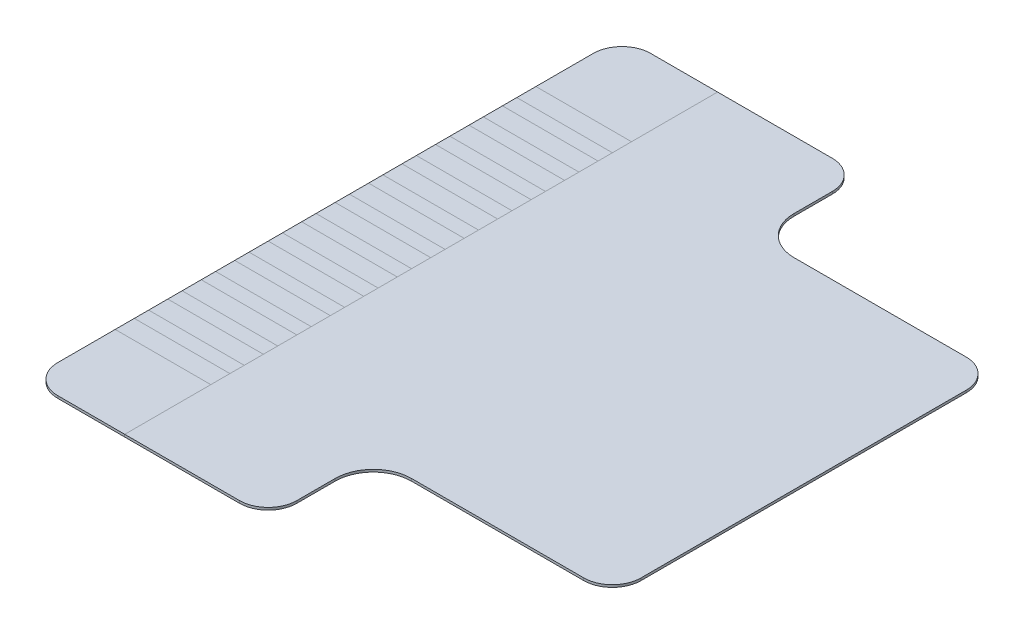
SolidWorks part; units mm, degrees
ref_plane "Front Plane" through (0, 0, 0) normal (0, 0, 1) x (1, 0, 0)
ref_plane "Top Plane" through (0, 0, 0) normal (0, 1, 0) x (1, 0, 0)
ref_plane "Right Plane" through (0, 0, 0) normal (1, 0, 0) x (0, 0, -1)
sketch "草图1" plane through (0, 0, 0) normal (0, 1, 0) x (1, 0, 0)
  line L0 (-7.3028, 0.9) -> (-7.3028, 0.5)
  line L1 (-6.7028, 6.2) -> (-2.9028, 6.2)
  line L2 (-7.3028, 5.6) -> (-7.3028, -5.6)
  line L3 (-6.7028, -6.2) -> (-2.9028, -6.2)
  line L4 (-2.3028, 5.6) -> (-2.3028, 4.8)
  line L5 (-1.5028, 4) -> (2.0972, 4)
  line L7 (-1.5028, -4) -> (2.0972, -4)
  line L8 (2.6972, 3.4) -> (2.6972, -3.4)
  line L9 (-7.3028, 0.2) -> (-5.3028, 0.2)
  line L10 (-7.3028, 0.2) -> (-7.3028, -0.2)
  line L11 (-7.3028, -0.2) -> (-5.3028, -0.2)
  line L12 (-5.3028, 0.2) -> (-5.3028, -0.2)
  line L13 (-7.3028, 0.9) -> (-5.3028, 0.9)
  line L14 (-5.3028, 0.9) -> (-5.3028, 0.5)
  line L15 (-7.3028, 0.5) -> (-5.3028, 0.5)
  line L16 (-7.3028, 1.6) -> (-7.3028, 1.2)
  line L17 (-7.3028, 1.6) -> (-5.3028, 1.6)
  line L18 (-5.3028, 1.6) -> (-5.3028, 1.2)
  line L19 (-7.3028, 1.2) -> (-5.3028, 1.2)
  line L20 (-7.3028, 2.3) -> (-7.3028, 1.9)
  line L21 (-7.3028, 2.3) -> (-5.3028, 2.3)
  line L22 (-5.3028, 2.3) -> (-5.3028, 1.9)
  line L23 (-7.3028, 1.9) -> (-5.3028, 1.9)
  line L24 (-7.3028, 3) -> (-7.3028, 2.6)
  line L25 (-7.3028, 3) -> (-5.3028, 3)
  line L26 (-5.3028, 3) -> (-5.3028, 2.6)
  line L27 (-7.3028, 2.6) -> (-5.3028, 2.6)
  line L28 (-7.3028, 3.7) -> (-7.3028, 3.3)
  line L29 (-7.3028, 3.7) -> (-5.3028, 3.7)
  line L30 (-5.3028, 3.7) -> (-5.3028, 3.3)
  line L31 (-7.3028, 3.3) -> (-5.3028, 3.3)
  line L32 (-7.3028, 4.4) -> (-7.3028, 4)
  line L33 (-7.3028, 4.4) -> (-5.3028, 4.4)
  line L34 (-5.3028, 4.4) -> (-5.3028, 4)
  line L35 (-7.3028, 4) -> (-5.3028, 4)
  line L36 (-7.3028, 0.2) -> (-7.3028, -0.2)
  line L37 (-7.3028, 0.2) -> (-5.3028, 0.2)
  line L38 (-5.3028, 0.2) -> (-5.3028, -0.2)
  line L39 (-7.3028, -0.2) -> (-5.3028, -0.2)
  line L40 (-7.3028, 0.9) -> (-7.3028, 0.5)
  line L41 (-7.3028, 0.9) -> (-5.3028, 0.9)
  line L42 (-5.3028, 0.9) -> (-5.3028, 0.5)
  line L43 (-7.3028, 0.5) -> (-5.3028, 0.5)
  line L44 (-7.3028, 1.6) -> (-7.3028, 1.2)
  line L45 (-7.3028, 1.6) -> (-5.3028, 1.6)
  line L46 (-5.3028, 1.6) -> (-5.3028, 1.2)
  line L47 (-7.3028, 1.2) -> (-5.3028, 1.2)
  line L48 (-7.3028, 2.3) -> (-7.3028, 1.9)
  line L49 (-7.3028, 2.3) -> (-5.3028, 2.3)
  line L50 (-5.3028, 2.3) -> (-5.3028, 1.9)
  line L51 (-7.3028, 1.9) -> (-5.3028, 1.9)
  line L52 (-7.3028, 3) -> (-7.3028, 2.6)
  line L53 (-7.3028, 3) -> (-5.3028, 3)
  line L54 (-5.3028, 3) -> (-5.3028, 2.6)
  line L55 (-7.3028, 2.6) -> (-5.3028, 2.6)
  line L56 (-7.3028, 3.7) -> (-7.3028, 3.3)
  line L57 (-7.3028, 3.7) -> (-5.3028, 3.7)
  line L58 (-5.3028, 3.7) -> (-5.3028, 3.3)
  line L59 (-7.3028, 3.3) -> (-5.3028, 3.3)
  line L60 (-7.3028, -0.5) -> (-7.3028, -0.9)
  line L61 (-7.3028, -0.5) -> (-5.3028, -0.5)
  line L62 (-5.3028, -0.5) -> (-5.3028, -0.9)
  line L63 (-7.3028, -0.9) -> (-5.3028, -0.9)
  line L64 (-7.3028, 0.2) -> (-7.3028, -0.2)
  line L65 (-7.3028, 0.2) -> (-5.3028, 0.2)
  line L66 (-5.3028, 0.2) -> (-5.3028, -0.2)
  line L67 (-7.3028, -0.2) -> (-5.3028, -0.2)
  line L68 (-7.3028, 0.9) -> (-7.3028, 0.5)
  line L69 (-7.3028, 0.9) -> (-5.3028, 0.9)
  line L70 (-5.3028, 0.9) -> (-5.3028, 0.5)
  line L71 (-7.3028, 0.5) -> (-5.3028, 0.5)
  line L72 (-7.3028, 1.6) -> (-7.3028, 1.2)
  line L73 (-7.3028, 1.6) -> (-5.3028, 1.6)
  line L74 (-5.3028, 1.6) -> (-5.3028, 1.2)
  line L75 (-7.3028, 1.2) -> (-5.3028, 1.2)
  line L76 (-7.3028, 2.3) -> (-7.3028, 1.9)
  line L77 (-7.3028, 2.3) -> (-5.3028, 2.3)
  line L78 (-5.3028, 2.3) -> (-5.3028, 1.9)
  line L79 (-7.3028, 1.9) -> (-5.3028, 1.9)
  line L80 (-7.3028, 3) -> (-7.3028, 2.6)
  line L81 (-7.3028, 3) -> (-5.3028, 3)
  line L82 (-5.3028, 3) -> (-5.3028, 2.6)
  line L83 (-7.3028, 2.6) -> (-5.3028, 2.6)
  line L84 (-7.3028, -1.2) -> (-7.3028, -1.6)
  line L85 (-7.3028, -1.2) -> (-5.3028, -1.2)
  line L86 (-5.3028, -1.2) -> (-5.3028, -1.6)
  line L87 (-7.3028, -1.6) -> (-5.3028, -1.6)
  line L88 (-7.3028, -0.5) -> (-7.3028, -0.9)
  line L89 (-7.3028, -0.5) -> (-5.3028, -0.5)
  line L90 (-5.3028, -0.5) -> (-5.3028, -0.9)
  line L91 (-7.3028, -0.9) -> (-5.3028, -0.9)
  line L92 (-7.3028, 0.2) -> (-7.3028, -0.2)
  line L93 (-7.3028, 0.2) -> (-5.3028, 0.2)
  line L94 (-5.3028, 0.2) -> (-5.3028, -0.2)
  line L95 (-7.3028, -0.2) -> (-5.3028, -0.2)
  line L96 (-7.3028, 0.9) -> (-7.3028, 0.5)
  line L97 (-7.3028, 0.9) -> (-5.3028, 0.9)
  line L98 (-5.3028, 0.9) -> (-5.3028, 0.5)
  line L99 (-7.3028, 0.5) -> (-5.3028, 0.5)
  line L100 (-7.3028, 1.6) -> (-7.3028, 1.2)
  line L101 (-7.3028, 1.6) -> (-5.3028, 1.6)
  line L102 (-5.3028, 1.6) -> (-5.3028, 1.2)
  line L103 (-7.3028, 1.2) -> (-5.3028, 1.2)
  line L104 (-7.3028, 2.3) -> (-7.3028, 1.9)
  line L105 (-7.3028, 2.3) -> (-5.3028, 2.3)
  line L106 (-5.3028, 2.3) -> (-5.3028, 1.9)
  line L107 (-7.3028, 1.9) -> (-5.3028, 1.9)
  line L108 (-7.3028, -1.9) -> (-7.3028, -2.3)
  line L109 (-7.3028, -1.9) -> (-5.3028, -1.9)
  line L110 (-5.3028, -1.9) -> (-5.3028, -2.3)
  line L111 (-7.3028, -2.3) -> (-5.3028, -2.3)
  line L112 (-7.3028, -1.2) -> (-7.3028, -1.6)
  line L113 (-7.3028, -1.2) -> (-5.3028, -1.2)
  line L114 (-5.3028, -1.2) -> (-5.3028, -1.6)
  line L115 (-7.3028, -1.6) -> (-5.3028, -1.6)
  line L116 (-7.3028, -0.5) -> (-7.3028, -0.9)
  line L117 (-7.3028, -0.5) -> (-5.3028, -0.5)
  line L118 (-5.3028, -0.5) -> (-5.3028, -0.9)
  line L119 (-7.3028, -0.9) -> (-5.3028, -0.9)
  line L120 (-7.3028, 0.2) -> (-7.3028, -0.2)
  line L121 (-7.3028, 0.2) -> (-5.3028, 0.2)
  line L122 (-5.3028, 0.2) -> (-5.3028, -0.2)
  line L123 (-7.3028, -0.2) -> (-5.3028, -0.2)
  line L124 (-7.3028, 0.9) -> (-7.3028, 0.5)
  line L125 (-7.3028, 0.9) -> (-5.3028, 0.9)
  line L126 (-5.3028, 0.9) -> (-5.3028, 0.5)
  line L127 (-7.3028, 0.5) -> (-5.3028, 0.5)
  line L128 (-7.3028, 1.6) -> (-7.3028, 1.2)
  line L129 (-7.3028, 1.6) -> (-5.3028, 1.6)
  line L130 (-5.3028, 1.6) -> (-5.3028, 1.2)
  line L131 (-7.3028, 1.2) -> (-5.3028, 1.2)
  line L132 (-7.3028, -2.6) -> (-7.3028, -3)
  line L133 (-7.3028, -2.6) -> (-5.3028, -2.6)
  line L134 (-5.3028, -2.6) -> (-5.3028, -3)
  line L135 (-7.3028, -3) -> (-5.3028, -3)
  line L136 (-7.3028, -1.9) -> (-7.3028, -2.3)
  line L137 (-7.3028, -1.9) -> (-5.3028, -1.9)
  line L138 (-5.3028, -1.9) -> (-5.3028, -2.3)
  line L139 (-7.3028, -2.3) -> (-5.3028, -2.3)
  line L140 (-7.3028, -1.2) -> (-7.3028, -1.6)
  line L141 (-7.3028, -1.2) -> (-5.3028, -1.2)
  line L142 (-5.3028, -1.2) -> (-5.3028, -1.6)
  line L143 (-7.3028, -1.6) -> (-5.3028, -1.6)
  line L144 (-7.3028, -0.5) -> (-7.3028, -0.9)
  line L145 (-7.3028, -0.5) -> (-5.3028, -0.5)
  line L146 (-5.3028, -0.5) -> (-5.3028, -0.9)
  line L147 (-7.3028, -0.9) -> (-5.3028, -0.9)
  line L148 (-7.3028, 0.2) -> (-7.3028, -0.2)
  line L149 (-7.3028, 0.2) -> (-5.3028, 0.2)
  line L150 (-5.3028, 0.2) -> (-5.3028, -0.2)
  line L151 (-7.3028, -0.2) -> (-5.3028, -0.2)
  line L152 (-7.3028, 0.9) -> (-7.3028, 0.5)
  line L153 (-7.3028, 0.9) -> (-5.3028, 0.9)
  line L154 (-5.3028, 0.9) -> (-5.3028, 0.5)
  line L155 (-7.3028, 0.5) -> (-5.3028, 0.5)
  line L156 (-7.3028, -3.3) -> (-7.3028, -3.7)
  line L157 (-7.3028, -3.3) -> (-5.3028, -3.3)
  line L158 (-5.3028, -3.3) -> (-5.3028, -3.7)
  line L159 (-7.3028, -3.7) -> (-5.3028, -3.7)
  line L160 (-7.3028, -2.6) -> (-7.3028, -3)
  line L161 (-7.3028, -2.6) -> (-5.3028, -2.6)
  line L162 (-5.3028, -2.6) -> (-5.3028, -3)
  line L163 (-7.3028, -3) -> (-5.3028, -3)
  line L164 (-7.3028, -1.9) -> (-7.3028, -2.3)
  line L165 (-7.3028, -1.9) -> (-5.3028, -1.9)
  line L166 (-5.3028, -1.9) -> (-5.3028, -2.3)
  line L167 (-7.3028, -2.3) -> (-5.3028, -2.3)
  line L168 (-7.3028, -1.2) -> (-7.3028, -1.6)
  line L169 (-7.3028, -1.2) -> (-5.3028, -1.2)
  line L170 (-5.3028, -1.2) -> (-5.3028, -1.6)
  line L171 (-7.3028, -1.6) -> (-5.3028, -1.6)
  line L172 (-7.3028, -0.5) -> (-7.3028, -0.9)
  line L173 (-7.3028, -0.5) -> (-5.3028, -0.5)
  line L174 (-5.3028, -0.5) -> (-5.3028, -0.9)
  line L175 (-7.3028, -0.9) -> (-5.3028, -0.9)
  line L176 (-7.3028, 0.2) -> (-7.3028, -0.2)
  line L177 (-7.3028, 0.2) -> (-5.3028, 0.2)
  line L178 (-5.3028, 0.2) -> (-5.3028, -0.2)
  line L179 (-7.3028, -0.2) -> (-5.3028, -0.2)
  line L180 (-7.3028, -0.5) -> (-7.3028, -0.9)
  line L181 (-7.3028, -0.5) -> (-5.3028, -0.5)
  line L182 (-5.3028, -0.5) -> (-5.3028, -0.9)
  line L183 (-7.3028, -0.9) -> (-5.3028, -0.9)
  line L184 (-7.3028, -1.2) -> (-7.3028, -1.6)
  line L185 (-7.3028, -1.2) -> (-5.3028, -1.2)
  line L186 (-5.3028, -1.2) -> (-5.3028, -1.6)
  line L187 (-7.3028, -1.6) -> (-5.3028, -1.6)
  line L188 (-7.3028, -1.9) -> (-7.3028, -2.3)
  line L189 (-7.3028, -1.9) -> (-5.3028, -1.9)
  line L190 (-5.3028, -1.9) -> (-5.3028, -2.3)
  line L191 (-7.3028, -2.3) -> (-5.3028, -2.3)
  line L192 (-7.3028, -2.6) -> (-7.3028, -3)
  line L193 (-7.3028, -2.6) -> (-5.3028, -2.6)
  line L194 (-5.3028, -2.6) -> (-5.3028, -3)
  line L195 (-7.3028, -3) -> (-5.3028, -3)
  line L196 (-7.3028, -3.3) -> (-7.3028, -3.7)
  line L197 (-7.3028, -3.3) -> (-5.3028, -3.3)
  line L198 (-5.3028, -3.3) -> (-5.3028, -3.7)
  line L199 (-7.3028, -3.7) -> (-5.3028, -3.7)
  line L200 (-7.3028, -4) -> (-7.3028, -4.4)
  line L201 (-7.3028, -4) -> (-5.3028, -4)
  line L202 (-5.3028, -4) -> (-5.3028, -4.4)
  line L203 (-7.3028, -4.4) -> (-5.3028, -4.4)
  line L204 (-2.3028, -4.8) -> (-2.3028, -5.6)
  line L205 (-5.3028, 6.2) -> (-5.3028, -6.2)
  arc A0 (2.0972, -4) -> (2.6972, -3.4) centre (2.0972, -3.4) ccw
  arc A1 (2.0972, 4) -> (2.6972, 3.4) centre (2.0972, 3.4) cw
  arc A2 (-2.9028, 6.2) -> (-2.3028, 5.6) centre (-2.9028, 5.6) cw
  arc A3 (-2.9028, -6.2) -> (-2.3028, -5.6) centre (-2.9028, -5.6) ccw
  arc A4 (-7.3028, -5.6) -> (-6.7028, -6.2) centre (-6.7028, -5.6) ccw
  arc A5 (-6.7028, 6.2) -> (-7.3028, 5.6) centre (-6.7028, 5.6) ccw
  arc A6 (-2.3028, -4.8) -> (-1.5028, -4) centre (-1.5028, -4.8) cw
  arc A7 (-1.5028, 4) -> (-2.3028, 4.8) centre (-1.5028, 4.8) cw
  point P12 (-5.3028, 0)
  point P14 (-7.3028, 0)
  point P15 (2.6972, 0)
  point P212 (2.6972, 4)
  point P215 (-2.3028, 6.2)
  point P220 (-7.3028, -6.2)
  point P223 (-7.3028, 6.2)
  point P228 (-2.3028, 4)
  dimension "D8" = 0.6
  dimension "D9" = 0.8
  dimension "D1" = 12.4
  dimension "D2" = 2
  dimension "D3" = 0.4
  dimension "D6" = 5
  dimension "D7" = 5
  dimension "D10" = 8
  dimension "D4" = 7
  dimension "D5" = 7
extrude "凸台-拉伸1" add sketch "草图1" along normal blind 0.05 contours L5 A7 L4 A2 L1 A5 L2 L33 L34 L35 L29 L30 L31 L25 L26 L27 L21 L22 L23 L17 L18 L19 L13 L14 L15 L9 L12 L11 L61 L62 L63 L85 L86 L87 L109 L110 L111 L133 L134 L135 region at (-1.7388, 0, 0)
extrude "凸台-拉伸2" add sketch "草图1<3>" along normal blind 0.05 separate body contours L2 L35 L34 L33 | L2 L31 L30 L29 | L2 L27 L26 L25 | L2 L23 L22 L21 | L2 L19 L18 L17 | L0 L15 L14 L13 | L12 L9 L2 L11 | L2 L63 L62 L61 | L2 L87 L86 L85 | L2 L111 L110 L109 | L2 L135 L134 L133 | L2 L159 L158 L157 | L201 L202 L203 L200 region at (-6.3028, 0, -0.7) region at (-6.3028, 0, -1.4) region at (-6.3028, 0, 0) region at (-6.3028, 0, -2.1) region at (-6.3028, 0, 0.7) region at (-6.3028, 0, -2.8) region at (-6.3028, 0, 1.4) region at (-6.3028, 0, -3.5) region at (-6.3028, 0, 2.1) region at (-6.3028, 0, -4.2) region at (-6.3028, 0, 2.8) region at (-6.3028, 0, 3.5)
sketch "草图1<3>" plane through (0, 0, 0) normal (0, 1, 0) x (1, 0, 0) same geometry as "草图1"
extrude "凸台-拉伸3" add sketch "草图1<5>" along normal blind 0.05 separate body contours L2 A4 L3 L205 L203 | L205 L159 L2 L201 | L205 L135 L2 L157 | L205 L111 L2 L133 | L205 L87 L2 L109 | L205 L63 L2 L85 | L205 L11 L2 L61 | L205 L15 L2 L9 | L205 L19 L2 L13 | L205 L23 L2 L17 | L1 A5 L2 L33 L205 | L205 L35 L2 L29 | L205 L31 L2 L25 | L205 L27 L2 L21 region at (-6.3028, 0, -1.05) region at (-6.3028, 0, -0.35) region at (-6.3028, 0, -1.75) region at (-6.3028, 0, 0.35) region at (-6.3028, 0, -2.45) region at (-6.3028, 0, 1.05) region at (-6.3028, 0, -3.15) region at (-6.3028, 0, 1.75) region at (-6.3028, 0, -3.85) region at (-6.3028, 0, 2.45) region at (-6.2838, 0, -5.2832) region at (-6.3028, 0, 3.15) region at (-6.3028, 0, 3.85) region at (-6.2838, 0, 5.2832)
sketch "草图1<5>" plane through (0, 0, 0) normal (0, 1, 0) x (1, 0, 0) same geometry as "草图1"
